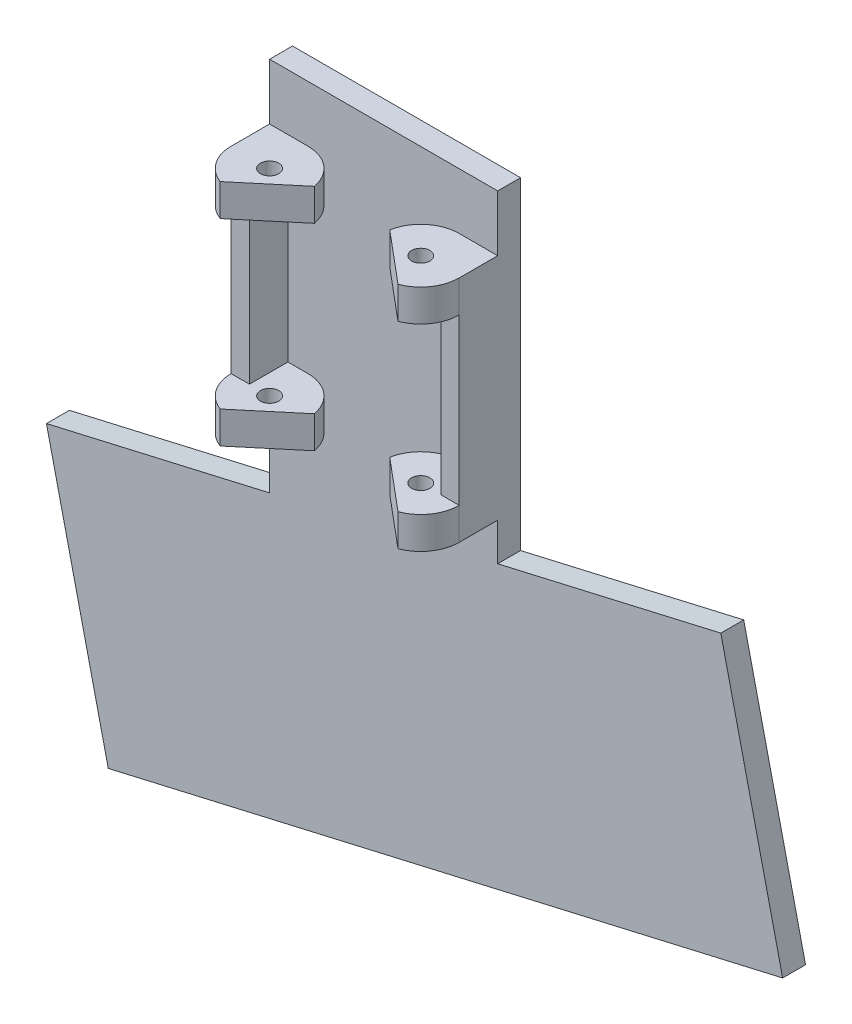
SolidWorks part; units mm, degrees
ref_plane "Front Plane" through (0, 0, 0) normal (0, 0, 1) x (1, 0, 0)
ref_plane "Top Plane" through (0, 0, 0) normal (0, 1, 0) x (1, 0, 0)
ref_plane "Right Plane" through (0, 0, 0) normal (1, 0, 0) x (0, 0, -1)
sketch "Sketch1" plane through (0, 0, 0) normal (0, 1, 0) x (1, 0, 0)
  line L0 (0, 22.8391) -> (0, -19.8342) construction
  line L1 (-35.1495, 0) -> (37.3645, 0) construction
  line L2 (-24.9, 0) -> (-24.9, 13.4)
  line L3 (-24.9, 13.4) -> (24.9, 13.4)
  line L4 (24.9, 0) -> (24.9, 13.4)
  line L5 (-19.4124, -7.879) -> (-8.235, 1.5)
  line L6 (19.4124, -7.879) -> (8.235, 1.5)
  line L7 (16.5, 8.4) -> (-16.5, 8.4)
  arc A0 (19.4124, -7.879) -> (24.9, 0) centre (16.5, 0) ccw
  arc A1 (-19.4124, -7.879) -> (-24.9, 0) centre (-16.5, 0) cw
  arc A2 (-16.5, 8.4) -> (-8.235, 1.5) centre (-16.5, 0) cw
  arc A3 (16.5, 8.4) -> (8.235, 1.5) centre (16.5, 0) ccw
  circle A4 centre (-16.5, 0) radius 8.4 construction
  circle A5 centre (16.5, 0) radius 8.4 construction
  point P14 (0, 13.4)
  point P16 (-20.4749, 7.4)
  dimension "D1" = 16.8
  dimension "D2" = 33
  dimension "D3" = 5
  dimension "D4" = 130
  dimension "D5" = 1.5
  dimension "D6" = 13.4
extrude "Boss-Extrude2" add sketch "Sketch1" along normal blind 7
sketch "Sketch3" plane through (0, 7, 0) normal (0, 1, 0) x (1, 0, 0)
  circle A0 centre (-16.5, 0) radius 2
  circle A1 centre (16.5, 0) radius 2
  dimension "D1" = 4
extrude "Cut-Extrude2" cut sketch "Sketch3" against normal through all both and the other way through all
sketch "Sketch4" plane through (0, 7, 0) normal (0, 1, 0) x (1, 0, 0)
  line L0 (-24.9, 13.4) -> (-24.9, 0)
  line L1 (-24.9, 13.4) -> (24.9, 13.4)
  line L2 (24.9, 13.4) -> (24.9, 0)
  line L3 (0, 13.4) -> (0, 0) construction
  line L4 (-16.5, 8.4) -> (16.5, 8.4)
  line L5 (-16.5, 8.4) -> (16.5, 8.4) construction
  line L6 (16.5, 8.4) -> (20.9, 8.4)
  line L7 (20.9, 8.4) -> (20.9, 0)
  line L8 (20.9, 0) -> (24.9, 0)
  line L9 (-20.9, 0) -> (-24.9, 0)
  line L10 (-20.9, 8.4) -> (-20.9, 0)
  line L11 (-16.5, 8.4) -> (-20.9, 8.4)
  circle A0 centre (-16.5, 0) radius 3.7 construction
  point P21 (0, 8.4)
  dimension "D2" = 7.4
  dimension "D1" = 4
extrude "Boss-Extrude3" add sketch "Sketch4" along normal blind 36
sketch "Sketch5" plane through (0, 43, 0) normal (0, 1, 0) x (1, 0, 0)
  line L12 (-24.9, 13.4) -> (-24.9, 0)
  line L13 (24.9, 13.4) -> (-24.9, 13.4)
  line L14 (24.9, 0) -> (24.9, 13.4)
  line L15 (8.235, 1.5) -> (19.4124, -7.879)
  line L16 (-16.5, 8.4) -> (16.5, 8.4)
  line L17 (-19.4124, -7.879) -> (-8.235, 1.5)
  line L18 (-24.9, 13.4) -> (-24.9, 0)
  line L19 (24.9, 13.4) -> (-24.9, 13.4)
  line L20 (24.9, 0) -> (24.9, 13.4)
  line L21 (8.235, 1.5) -> (19.4124, -7.879)
  line L22 (-16.5, 8.4) -> (16.5, 8.4)
  line L23 (-19.4124, -7.879) -> (-8.235, 1.5)
  circle A0 centre (-16.5, 0) radius 2 construction
  circle A1 centre (16.5, 0) radius 2
  circle A2 centre (16.5, 0) radius 2 construction
  circle A4 centre (-16.5, 0) radius 2
  arc A8 (-24.9, 0) -> (-19.4124, -7.879) centre (-16.5, 0) ccw
  arc A9 (19.4124, -7.879) -> (24.9, 0) centre (16.5, 0) ccw
  arc A10 (16.5, 8.4) -> (8.235, 1.5) centre (16.5, 0) ccw
  arc A11 (-8.235, 1.5) -> (-16.5, 8.4) centre (-16.5, 0) ccw
  arc A12 (-24.9, 0) -> (-19.4124, -7.879) centre (-16.5, 0) ccw
  arc A13 (19.4124, -7.879) -> (24.9, 0) centre (16.5, 0) ccw
  arc A14 (16.5, 8.4) -> (8.235, 1.5) centre (16.5, 0) ccw
  arc A15 (-8.235, 1.5) -> (-16.5, 8.4) centre (-16.5, 0) ccw
  dimension "D1" = 0
extrude "Boss-Extrude4" add sketch "Sketch5" along normal blind 7
sketch "Sketch13" plane through (0, 50, 0) normal (0, 1, 0) x (1, 0, 0)
  line L0 (24.9, 0) -> (24.9, 13.4) construction
  line L5 (-24.9, 13.4) -> (24.9, 13.4)
  line L6 (-24.9, 13.4) -> (-24.9, 8.4)
  line L7 (-24.9, 8.4) -> (24.9, 8.4)
  line L8 (24.9, 13.4) -> (24.9, 8.4)
  line L9 (-16.5, 8.4) -> (16.5, 8.4) construction
extrude "Boss-Extrude6" add sketch "Sketch13" along normal blind 12.25
sketch "Sketch15" plane through (0, 0, 0) normal (0, -1, 0) x (1, 0, 0)
  line L0 (24.9, 0) -> (24.9, -13.4) construction
  line L1 (-24.9, -13.4) -> (24.9, -13.4)
  line L2 (-24.9, -13.4) -> (-24.9, -8.4)
  line L3 (-24.9, -8.4) -> (24.9, -8.4)
  line L4 (24.9, -13.4) -> (24.9, -8.4)
  line L5 (-16.5, -8.4) -> (16.5, -8.4) construction
extrude "Boss-Extrude7" add sketch "Sketch15" along normal blind 8.25
sketch "Sketch12" plane through (0, 0, -13.4) normal (0, 0, -1) x (-1, 0, 0)
  line L11 (24.9, -8.25) -> (24.9, -19.7472)
  line L12 (-24.9, -8.25) -> (24.9, -8.25)
  line L14 (-24.9, -8.25) -> (-73.6185, 2.9976)
  line L15 (-73.6185, 2.9976) -> (-87.1156, -55.4647)
  line L16 (-87.1156, -55.4647) -> (60.1214, -89.457)
  line L17 (60.1214, -89.457) -> (73.6185, -30.9948)
  line L18 (73.6185, -30.9948) -> (24.9, -19.7472)
  point P2 (0, 0)
  point P5 (77.4876, -31.888)
  point P10 (0, 0)
  dimension "D1" = 13
  dimension "D2" = 60
  dimension "D3" = 50
  dimension "D4" = 50
extrude "Boss-Extrude8" add sketch "Sketch12" against normal blind 5
